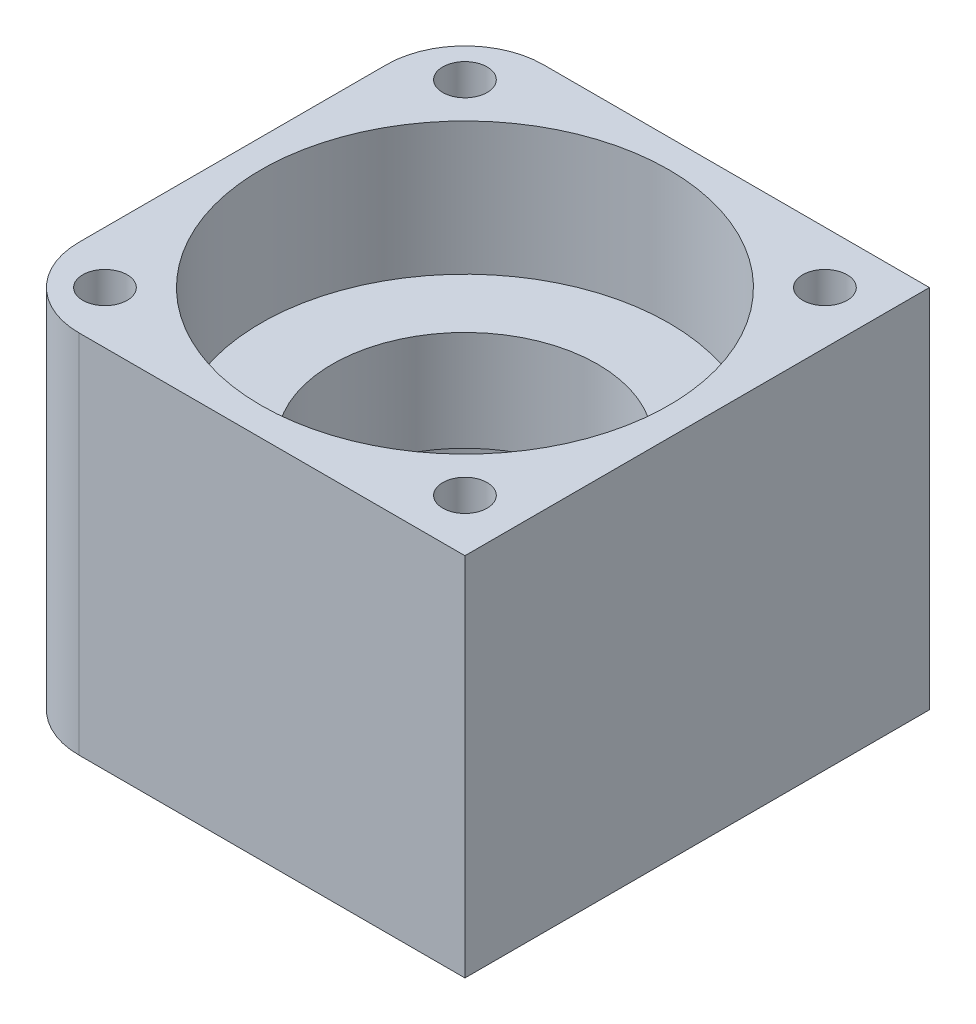
SolidWorks part; units mm, degrees
ref_plane "Front Plane" through (0, 0, 0) normal (0, 0, 1) x (1, 0, 0)
ref_plane "Top Plane" through (0, 0, 0) normal (0, 1, 0) x (1, 0, 0)
ref_plane "Right Plane" through (0, 0, 0) normal (1, 0, 0) x (0, 0, -1)
sketch "Sketch1" plane through (0, 0, 0) normal (0, 1, 0) x (1, 0, 0)
  line L1 (0, 0) -> (88.9, 0)
  line L2 (0, 0) -> (0, 88.9)
  line L3 (0, 88.9) -> (88.9, 88.9)
  line L4 (88.9, 0) -> (88.9, 88.9)
  line L5 (10, 10) -> (78.9, 10)
  line L6 (10, 10) -> (10, 78.9)
  line L7 (10, 78.9) -> (78.9, 78.9)
  line L8 (78.9, 10) -> (78.9, 78.9)
  circle A0 centre (78.9, 78.9) radius 4.25
  circle A1 centre (78.9, 10) radius 4.25
  circle A2 centre (10, 10) radius 4.25
  circle A3 centre (10, 78.9) radius 4.25
  dimension "D1" = 88.9
  dimension "D2" = 88.9
  dimension "D3" = 10
  dimension "D4" = 10
  dimension "D5" = 10
  dimension "D6" = 10
extrude "Boss-Extrude1" add sketch "Sketch1" along normal blind 70 contours L1 L4 L3 L2 A3 L7 A0 L8 A1 L5 A2 L6 | A3 L6 A2 L5 A1 L8 A0 L7 region at (1.2572, 0, -44.45) region at (44.45, 0, -44.45)
sketch "Sketch2" plane through (0, 70, 0) normal (0, 1, 0) x (1, 0, 0)
  circle A0 centre (44.45, 44.45) radius 25.4
extrude "Cut-Extrude1" cut sketch "Sketch2" against normal blind 70
sketch "Sketch3" plane through (0, 70, 0) normal (0, 1, 0) x (1, 0, 0)
  circle A0 centre (44.45, 44.45) radius 39.05
extrude "Cut-Extrude2" cut sketch "Sketch3" against normal blind 25.4
sketch "Sketch4" plane through (0, 0, 0) normal (0, -1, 0) x (1, 0, 0)
  circle A0 centre (44.45, -44.45) radius 39.05
extrude "Cut-Extrude3" cut sketch "Sketch4" against normal blind 25.4
fillet "Fillet1" radius 15 2 edges at (0, 35, 0) (0, 35, -88.9)
